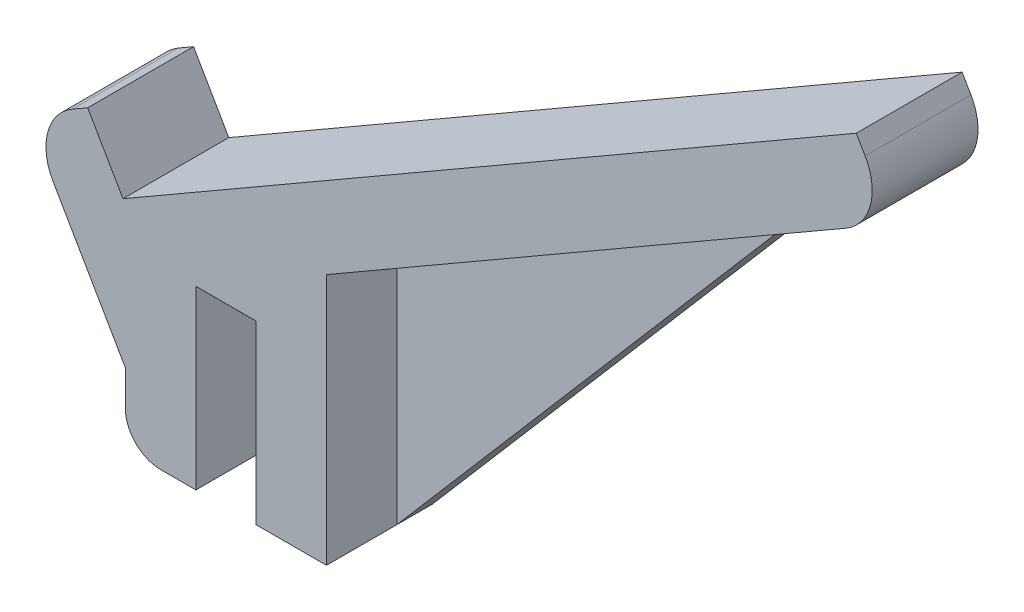
SolidWorks part; units mm, degrees
ref_plane "Front Plane" through (0, 0, 0) normal (0, 0, 1) x (1, 0, 0)
ref_plane "Top Plane" through (0, 0, 0) normal (0, 1, 0) x (1, 0, 0)
ref_plane "Right Plane" through (0, 0, 0) normal (1, 0, 0) x (0, 0, -1)
sketch "Sketch1" plane through (0, 0, 0) normal (0, 0, 1) x (1, 0, 0)
  line L0 (0, 0) -> (0, -50)
  line L1 (0, -50) -> (20, -50)
  line L2 (20, -50) -> (20, 21.362)
  line L3 (20, 21.362) -> (180.1762, 113.8397)
  line L4 (0, 0) -> (-17, 0)
  line L5 (-17, 0) -> (-17, -50)
  line L6 (-17, -50) -> (-37, -50)
  line L7 (-37, -50) -> (-37, -30)
  line L8 (-37, -30) -> (-64.9904, 18.4808)
  line L9 (-64.9904, 18.4808) -> (-47.6699, 28.4808)
  line L10 (-47.6699, 28.4808) -> (-37.6699, 11.1603)
  line L11 (-37.6699, 11.1603) -> (170.1762, 131.1603)
  line L12 (170.1762, 131.1603) -> (180.1762, 113.8397)
  line L13 (-17, -50) -> (0, -50) construction
  point P9 (0, 0)
  point P11 (-41.5322, -1.807)
  point P14 (-33.7034, 6.7855)
  point P17 (183.2325, 108.5461)
  dimension "D1" = 17
  dimension "D2" = 20
  dimension "D3" = 20
  dimension "D4" = 20
  dimension "D5" = 20
  dimension "D6" = 240
  dimension "D7" = 50
  dimension "D8" = 20
  dimension "D9" = 30
  dimension "D10" = 20
  dimension "D11" = 20
extrude "Boss-Extrude1" add sketch "Sketch1" along normal blind 30
sketch "Sketch2" plane through (0, 0, 0) normal (0, 0, 1) x (1, 0, 0)
  line L0 (20, -50) -> (141.4853, 91.5016)
  line L1 (20, 21.362) -> (180.1762, 113.8397) construction
  line L2 (141.4853, 91.5016) -> (20, 21.362)
  line L3 (20, 21.362) -> (20, -50)
extrude "Boss-Extrude2" add sketch "Sketch2" along normal blind 10
fillet "Fillet1" radius 15 1 edges at (-64.9904, 18.4808, 15)
fillet "Fillet2" radius 10 1 edges at (-37, -50, 15)
fillet "Fillet3" radius 15 1 edges at (180.1762, 113.8397, 15)
